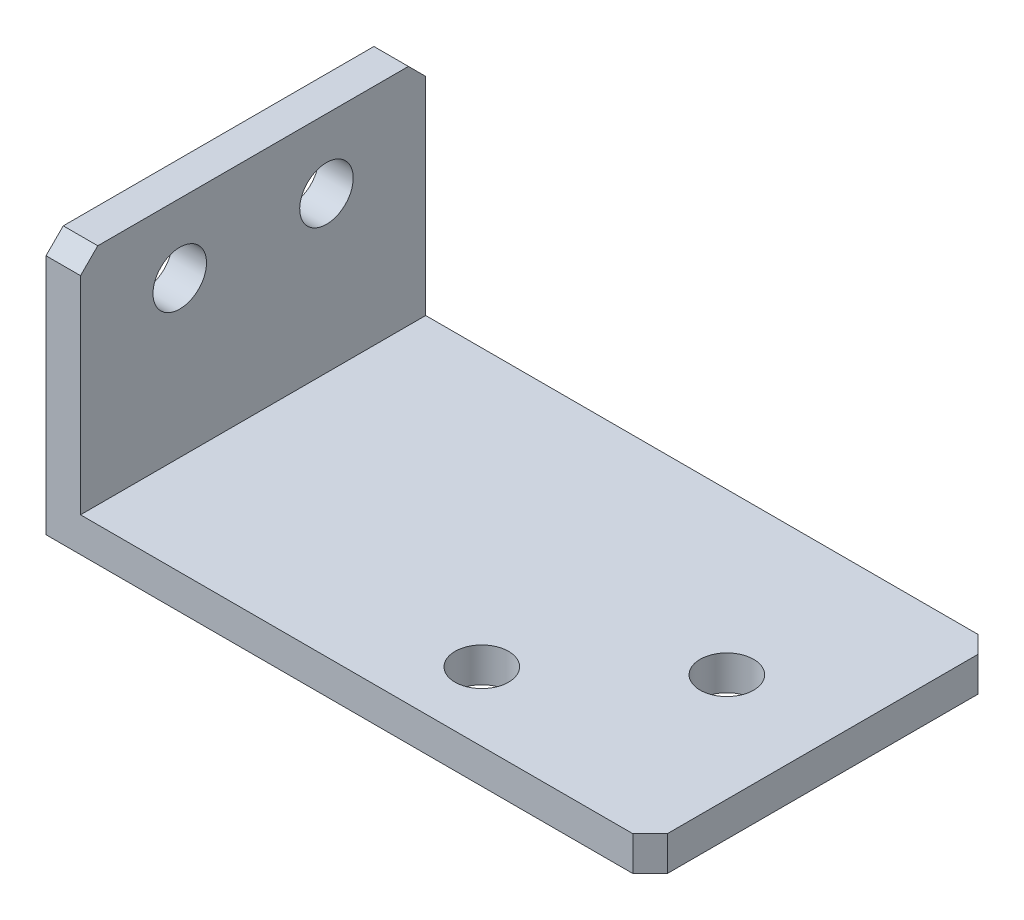
SolidWorks part; units mm, degrees
material "6063-T5"
ref_plane "Спереди" through (0, 0, 0) normal (0, 0, 1) x (1, 0, 0)
ref_plane "Сверху" through (0, 0, 0) normal (0, 1, 0) x (1, 0, 0)
ref_plane "Справа" through (0, 0, 0) normal (1, 0, 0) x (0, 0, -1)
sketch "Sketch1" plane through (0, 0, 0) normal (0, 0, 1) x (1, 0, 0)
  line L0 (0, 0) -> (35, 0)
  line L1 (35, 0) -> (35, 2)
  line L2 (35, 2) -> (2, 2)
  line L3 (2, 2) -> (2, 15)
  line L4 (2, 15) -> (0, 15)
  line L5 (0, 15) -> (0, 0)
  dimension "D1" = 35
  dimension "D2" = 15
  dimension "D4" = 2
extrude "Base" add sketch "Sketch1" along normal blind 20
sketch "Sketch2" plane through (0, 0, 0) normal (-1, 0, 0) x (0, 0, 1)
  line L2 (20, 0) -> (0, 0) construction
  line L3 (10, 0) -> (10, 14.2922) construction
  circle A0 centre (14.25, 11) radius 1.55
  circle A1 centre (5.75, 11) radius 1.55
  dimension "D5" = 3.1
  dimension "D1" = 8.5
  dimension "D3" = 11
extrude "CarriageSide" cut sketch "Sketch2" against normal up to surface (2 mm away) up to face at (2, 8.5, 10)
sketch "Sketch5" plane through (0, 2, 0) normal (0, 1, 0) x (1, 0, 0)
  line L0 (0, -20) -> (0, 0) construction
  line L2 (35, -20) -> (2, -20) construction
  circle A0 centre (21.25, -16) radius 1.55
  circle A1 centre (28.75, -9.3) radius 1.55
  dimension "D3" = 3.1
  dimension "D1" = 4
  dimension "D2" = 6.7
  dimension "D4" = 7.5
  dimension "D5" = 21.25
extrude "CableChainSide" cut sketch "Sketch5" against normal through all
chamfer "Chamfer1" distance 1 angle 45 4 edges at (35, 1, 0) (1, 15, 0) (1, 15, 20) (35, 1, 20)
